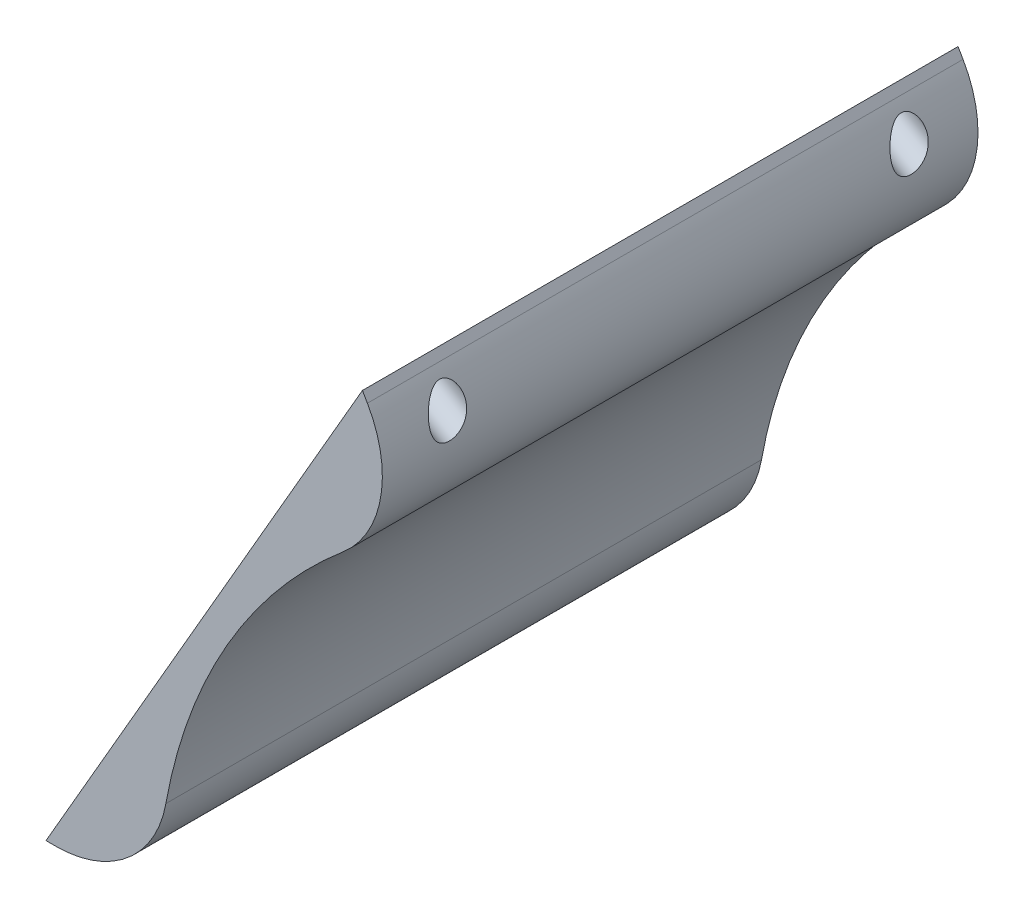
SolidWorks part; units mm, degrees
ref_plane "Front Plane" through (0, 0, 0) normal (0, 0, 1) x (1, 0, 0)
ref_plane "Top Plane" through (0, 0, 0) normal (0, 1, 0) x (1, 0, 0)
ref_plane "Right Plane" through (0, 0, 0) normal (1, 0, 0) x (0, 0, -1)
sketch "Sketch2" plane through (0, 0, 0) normal (0, 0, 1) x (1, 0, 0)
  line L2 (-70, 0) -> (-85, 0)
  line L3 (-35, 60.6218) -> (-42.5, 73.6122)
  line L4 (-85, 0) -> (-42.5, 73.6122)
  arc A0 (-70, 0) -> (-35, 60.6218) centre (0, 0) cw
  point P6 (-60.6218, 35)
  dimension "D2" = 70
  dimension "D1" = 30
  dimension "D3" = 15
  dimension "D4" = 15
extrude "Boss-Extrude1" add sketch "Sketch2" along normal blind 80 contours L2 L4 L3 A0
fillet "Fillet1" radius 15 1 edges at (-70, 0, 40)
fillet "Fillet2" radius 15 1 edges at (-35, 60.6218, 40)
sketch "Sketch3" plane through (-63.75, 36.8061, 0) normal (-0.866, 0.5, 0) x (0, 0, 1)
  line L0 (80, 42.5) -> (0, 42.5) construction
  line L1 (0, -42.5) -> (0, 42.5) construction
  circle A0 centre (9, 38.5) radius 2.5
  dimension "D1" = 5
  dimension "D2" = 4
  dimension "D3" = 9
extrude "Cut-Extrude1" cut sketch "Sketch3" against normal blind 10
extrude "Boss-Extrude2" add sketch "Sketch3<2>" against normal blind 1
sketch "Sketch3<2>" plane through (-63.75, 36.8061, 0) normal (-0.866, 0.5, 0) x (0, 0, 1) same geometry as "Sketch3"
sketch "Sketch5" plane through (-63.75, 36.8061, 0) normal (-0.866, 0.5, 0) x (0, 0, 1)
  line L0 (0, -42.5) -> (0, 42.5) construction
  line L1 (80, 42.5) -> (0, 42.5) construction
  circle A0 centre (9, 38.5) radius 1.5
  dimension "D3" = 3
  dimension "D1" = 9
  dimension "D2" = 4
extrude "Cut-Extrude2" cut sketch "Sketch5" against normal blind 1 contours A0
pattern_linear "LPattern1" count 2 spacing 62 along (0, 0, 1) of "Cut-Extrude1", "Boss-Extrude2", "Cut-Extrude2"
pattern_linear "LPattern2" count 2 spacing 77 along (-0.5, -0.866, 0) of "LPattern1", "Cut-Extrude1", "Boss-Extrude2", "Cut-Extrude2"
